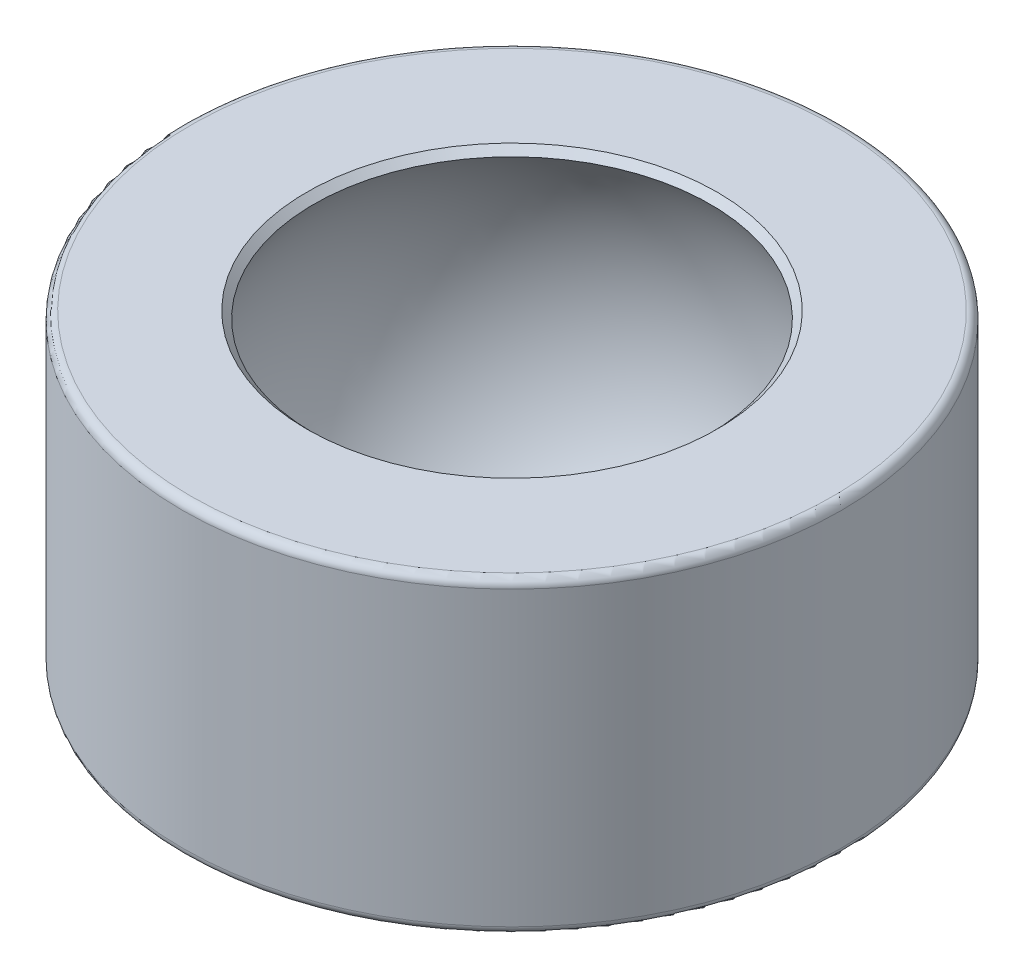
SolidWorks part; units mm, degrees
ref_plane "Front Plane" through (0, 0, 0) normal (0, 0, 1) x (1, 0, 0)
ref_plane "Top Plane" through (0, 0, 0) normal (0, 1, 0) x (1, 0, 0)
ref_plane "Right Plane" through (0, 0, 0) normal (1, 0, 0) x (0, 0, -1)
sketch "Sketch1" plane through (0, 0, 0) normal (0, 1, 0) x (1, 0, 0)
  circle A0 centre (0, 0) radius 4
  circle A1 centre (0, 0) radius 3 construction
  circle A2 centre (0, 0) radius 2
  dimension "D1" = 8
  dimension "D2" = 6
  dimension "D3" = 4
extrude "Boss-Extrude1" add sketch "Sketch1" along normal blind 1.875 and the other way blind 1.875
sketch "Sketch2" plane through (0, 0, 0) normal (0, 1, 0) x (1, 0, 0)
  line L0 (0, 3) -> (0, -3)
  circle A0 centre (0, 0) radius 3 construction
  arc A1 (0, 3) -> (0, -3) centre (0, 0) ccw
revolve "Revolve1" add sketch "Sketch2" angle 360 about L0 region at (-1.2732, 0, 0)
combine bodies "Combine1" operation type subtract main body 101 bodies to subtract 102
fillet "Fillet2" radius 0.1 2 edges at (0, 1.875, 4) (0, -1.875, 4)
chamfer "Chamfer2" distance 0.15 angle 45 2 edges at (0, -1.875, 2.3419) (0, 1.875, 2.3419) first distance on face at (0, 1.875, 2.3419) first distance on face at (0, 1.875, 3.9)
